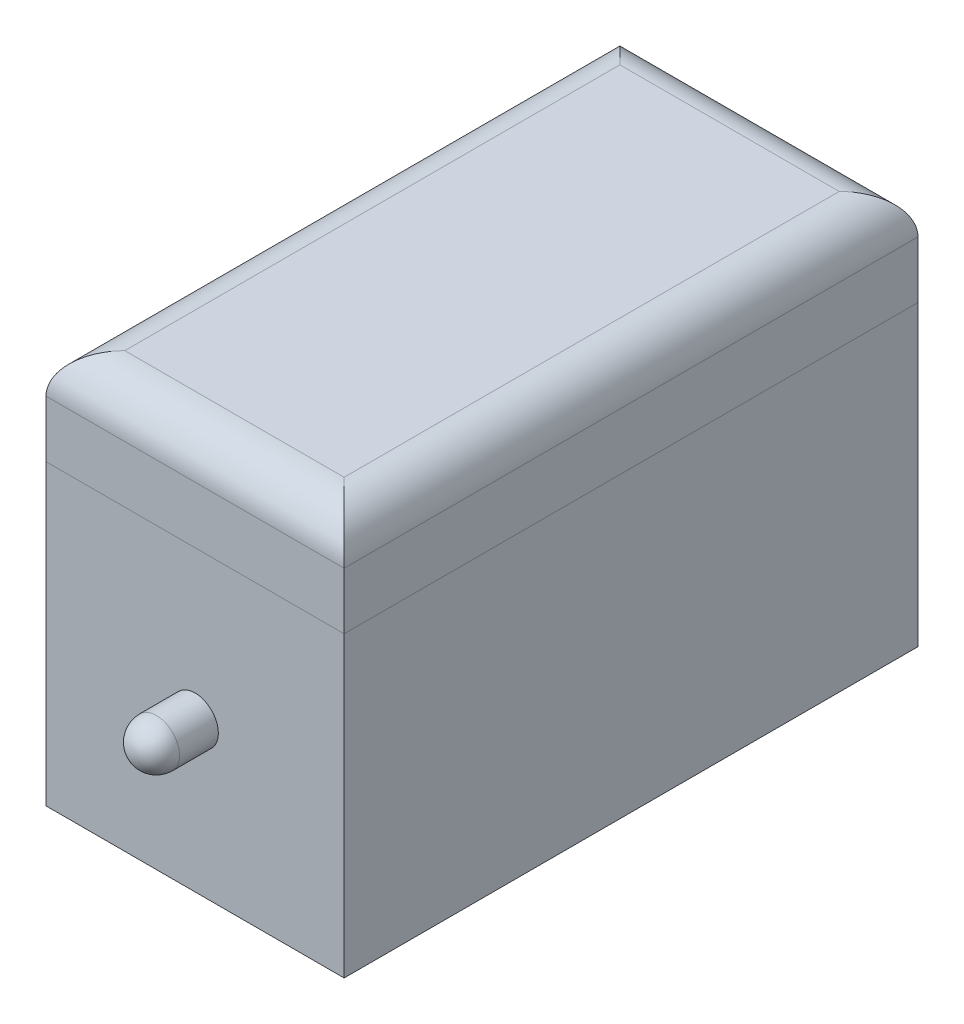
SolidWorks part; units mm, degrees
ref_plane "Front Plane" through (0, 0, 0) normal (0, 0, 1) x (1, 0, 0)
ref_plane "Top Plane" through (0, 0, 0) normal (0, 1, 0) x (1, 0, 0)
ref_plane "Right Plane" through (0, 0, 0) normal (1, 0, 0) x (0, 0, -1)
sketch "Sketch1" plane through (0, 0, 0) normal (0, 0, 1) x (1, 0, 0)
  line L1 (-9.61, 9.61) -> (9.61, 9.61)
  line L2 (-9.61, 9.61) -> (-9.61, -9.61)
  line L3 (-9.61, -9.61) -> (9.61, -9.61)
  line L4 (9.61, 9.61) -> (9.61, -9.61)
  line L5 (-9.61, 9.61) -> (9.61, -9.61) construction
  line L6 (-9.61, -9.61) -> (9.61, 9.61) construction
  point P0 (0, 0)
  dimension "D1" = 19.22
  dimension "D2" = 19.22
extrude "Boss-Extrude1" add sketch "Sketch1" along normal blind 37
sketch "Sketch3" plane through (0, 0, 37) normal (0, 0, 1) x (1, 0, 0)
  line L0 (0, -9.61) -> (0, 9.61) construction
  line L1 (-9.61, -9.61) -> (9.61, -9.61) construction
  line L2 (9.61, 9.61) -> (-9.61, 9.61) construction
  line L3 (-9.61, 0) -> (9.61, 0) construction
  line L4 (-9.61, 9.61) -> (-9.61, -9.61) construction
  line L5 (9.61, -9.61) -> (9.61, 9.61) construction
  circle A0 centre (0, 0) radius 1.5
  dimension "D1" = 3
extrude "Boss-Extrude2" add sketch "Sketch3" along normal blind 2.5
dome "Dome1" faces to dome 1 distance 1.5 reverse direction no elliptical dome no face at (1.5, 0, 39.5) parameters "D1"=1.5
sketch "Sketch4" plane through (0, 9.61, 0) normal (0, 1, 0) x (1, 0, 0)
  line L4 (9.61, 0) -> (-9.61, 0)
  line L5 (-9.61, 0) -> (-9.61, -37)
  line L6 (-9.61, -37) -> (9.61, -37)
  line L7 (9.61, -37) -> (9.61, 0)
  line L8 (9.61, 0) -> (-9.61, 0)
  line L9 (-9.61, 0) -> (-9.61, -37)
  line L10 (-9.61, -37) -> (9.61, -37)
  line L11 (9.61, -37) -> (9.61, 0)
  dimension "D1" = 0
extrude "Boss-Extrude3" add sketch "Sketch4" along normal blind 6.2 separate body
fillet "Fillet1" radius 2.54 4 edges at (0, 15.81, 37) (-9.61, 15.81, 18.5) (0, 15.81, 0) (9.61, 15.81, 18.5)
